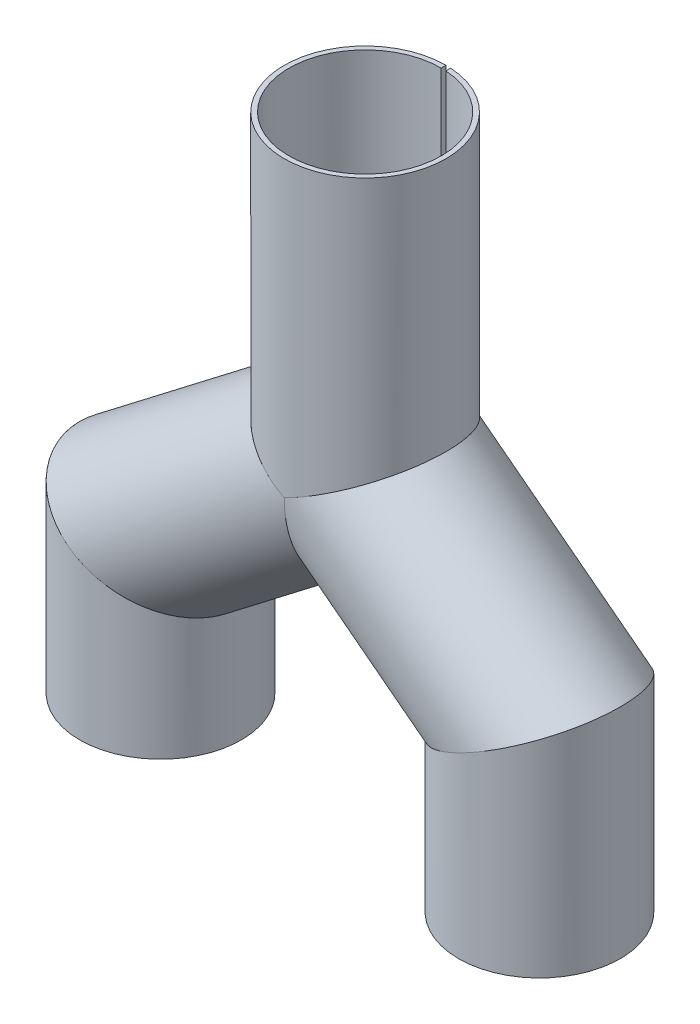
SolidWorks part; units mm, degrees
ref_plane "前视基准面" through (0, 0, 0) normal (0, 0, 1) x (1, 0, 0)
ref_plane "上视基准面" through (0, 0, 0) normal (0, 1, 0) x (1, 0, 0)
ref_plane "右视基准面" through (0, 0, 0) normal (1, 0, 0) x (0, 0, -1)
sketch "草图1" plane through (0, 0, 0) normal (0, 0, 1) x (1, 0, 0)
  line L0 (0, 0) -> (0, 61.6153) construction
  line L1 (-42.9378, -32.9568) -> (0, 0) construction
  line L2 (0, 0) -> (36.5871, -28.0823) construction
  line L3 (0, 0) -> (0, -65.4897) construction
  line L4 (0, -65.4897) -> (0, -66.4897) construction
  line L5 (-16.9772, 61.6153) -> (16.9772, 61.6153) construction
  line L6 (-42.9378, -32.9568) -> (-42.9378, -65.4897) construction
  line L7 (36.5871, -28.0823) -> (36.5871, -65.4897) construction
  line L8 (19.6099, -65.4897) -> (53.5642, -65.4897) construction
  line L9 (19.6099, -36.4531) -> (53.5642, -19.7116) construction
  line L10 (-25.9606, -41.3275) -> (-59.9149, -24.586) construction
  line L11 (-59.9149, -65.4897) -> (-25.9606, -65.4897) construction
  line L12 (16.9772, 61.6153) -> (16.9772, 8.3708) construction
  line L13 (16.9772, 8.3708) -> (53.5642, -19.7116) construction
  line L14 (53.5642, -19.7116) -> (53.5642, -65.4897) construction
  line L15 (19.6099, -65.4897) -> (19.6099, -36.4531) construction
  line L16 (19.6099, -36.4531) -> (0, -21.4015) construction
  line L17 (0, -21.4015) -> (-25.9606, -41.3275) construction
  line L18 (19.6099, -36.4531) -> (40.2837, -9.5181) construction
  line L19 (-16.9772, 61.6153) -> (-16.9772, 8.3708) construction
  line L20 (-16.9772, 8.3708) -> (-59.9149, -24.586) construction
  line L21 (-59.9149, -24.586) -> (-59.9149, -65.4897) construction
  line L22 (-25.9606, -41.3275) -> (-46.6344, -14.3926) construction
  line L23 (-16.9772, 8.3708) -> (0, 0) construction
  line L24 (0, 0) -> (16.9772, 8.3708) construction
  line L25 (-25.9606, -41.3275) -> (-25.9606, -65.4897) construction
  line L26 (0, 0) -> (0, 61.6153)
  dimension "t" = 1
  dimension "L1" = 61.6153
  dimension "R" = 16.9772
  dimension "L2" = 32.5329
  dimension "L4" = 42.9378
  dimension "L5" = 36.5871
  dimension "B" = 104.984
  dimension "B/2" = 52.492
sketch "草图2" plane through (0, 0, 0) normal (0, 1, 0) x (1, 0, 0)
  circle A0 centre (0, 0) radius 16.9772
extrude "拉伸-薄壁1" add sketch "草图2" along normal up to vertex (61.6153 mm away) thin up to point (0, 61.6153, 0) thin type one direction reverse wall 1
ref_plane "基准面1" through (36.5871, -28.0823, 0) normal (0.7933, -0.6089, 0) x (0, 0, -1)
sketch "草图3" plane through (36.5871, -28.0823, 0) normal (0.7933, -0.6089, 0) x (0, 0, -1)
  circle A0 centre (0, 0) radius 16.9772
extrude "拉伸-薄壁2" add sketch "草图3" against normal up to vertex (46.1219 mm away) and the other way up to vertex (8.3708 mm away) separate body thin up to point (0, 0, 0) other way up to point (53.5642, -19.7116, 0) thin type one direction reverse wall 1
ref_plane "基准面2" through (0, -65.4897, 0) normal (0, 1, 0) x (-1, 0, 0)
sketch "草图4" plane through (0, -65.4897, 0) normal (0, 1, 0) x (-1, 0, 0)
  line L0 (-19.6099, 0) -> (-53.5642, 0) construction
  circle A0 centre (-36.5871, 0) radius 16.9772
extrude "拉伸-薄壁3" add sketch "草图4" along normal up to vertex (45.7781 mm away) separate body thin up to point (53.5642, -19.7116, 0) thin type one direction reverse wall 1
ref_plane "基准面3" through (-42.9378, -32.9568, 0) normal (0.7933, 0.6089, 0) x (0, 0, -1)
sketch "草图5" plane through (-42.9378, -32.9568, 0) normal (0.7933, 0.6089, 0) x (0, 0, -1)
  circle A0 centre (0, 0) radius 16.9772
extrude "拉伸-薄壁4" add sketch "草图5" along normal up to vertex (54.1276 mm away) and the other way up to vertex (8.3708 mm away) separate body thin up to point (0, 0, 0) other way up to point (-59.9149, -24.586, 0) thin type one direction reverse wall 1
sketch "草图6" plane through (0, -65.4897, 0) normal (0, 1, 0) x (-1, 0, 0)
  circle A0 centre (42.9378, 0) radius 16.9772
extrude "拉伸-薄壁5" add sketch "草图6" along normal up to vertex (40.9036 mm away) separate body thin up to point (-59.9149, -24.586, 0) thin type one direction reverse wall 1
sketch "草图7" plane through (0, 0, 0) normal (0, 0, 1) x (1, 0, 0)
  line L0 (-33.9544, 16.7415) -> (0, 0)
  line L1 (0, 0) -> (33.9544, 16.7415)
  line L2 (33.9544, 16.7415) -> (33.9544, -19.7116)
  line L3 (33.9544, -19.7116) -> (-33.9544, -19.7116)
  line L4 (-33.9544, -19.7116) -> (-33.9544, 16.7415)
extrude "切除-拉伸1" cut sketch "草图7" against normal through all and the other way through all
sketch "草图8" plane through (0, 0, 0) normal (0, 0, 1) x (1, 0, 0)
  line L0 (-59.9149, -24.586) -> (-25.9606, -41.3275)
  line L2 (19.6099, -36.4531) -> (53.5642, -19.7116)
  line L3 (-59.9149, -24.586) -> (-59.9149, -66.4897)
  line L4 (-59.9149, -66.4897) -> (53.5642, -66.4897)
  line L5 (53.5642, -66.4897) -> (53.5642, -19.7116)
  line L6 (-25.9606, -41.3275) -> (-25.9606, -65.4897)
  line L7 (-25.9606, -65.4897) -> (19.6099, -65.4897)
  line L8 (19.6099, -65.4897) -> (19.6099, -36.4531)
extrude "切除-拉伸2" cut sketch "草图8" against normal through all and the other way through all
sketch "草图9" plane through (0, 0, 0) normal (0, 0, 1) x (1, 0, 0)
  line L0 (-16.9772, 8.3708) -> (0, 0) construction
  line L1 (-16.9772, 8.3708) -> (-16.9772, 61.6153)
  line L2 (0, 0) -> (0, -65.4897) construction
  line L3 (-16.9772, 61.6153) -> (16.9772, 61.6153)
  line L4 (16.9772, 61.6153) -> (16.9772, -65.4897)
  line L5 (-16.9772, 8.3708) -> (0, 0)
  line L6 (0, 0) -> (0, -65.4897)
  line L7 (0, -65.4897) -> (16.9772, -65.4897)
extrude "切除-拉伸3" cut sketch "草图9" against normal through all and the other way through all
sketch "草图10" plane through (0, 0, 0) normal (0, 0, 1) x (1, 0, 0)
  line L0 (16.9772, 8.3708) -> (16.9772, 61.6153)
  line L1 (16.9772, 61.6153) -> (-16.9772, 61.6153)
  line L2 (-16.9772, 61.6153) -> (-16.9772, -65.4897)
  line L3 (0, 0) -> (16.9772, 8.3708) construction
  line L4 (0, 0) -> (16.9772, 8.3708)
  line L5 (0, 0) -> (0, -65.4897) construction
  line L6 (0, 0) -> (0, -65.4897)
  line L7 (0, -65.4897) -> (-16.9772, -65.4897)
extrude "切除-拉伸6" cut sketch "草图10" against normal through all and the other way through all
extrude "切除-拉伸5" cut sketch "草图8<2>" against normal through all and the other way through all flip side to cut
sketch "草图8<2>" plane through (0, 0, 0) normal (0, 0, 1) x (1, 0, 0) same geometry as "草图8"
sketch "草图11" plane through (0, 0, 0) normal (0, 0, 1) x (1, 0, 0)
  line L0 (-42.9378, -32.9568) -> (0, 0) construction
  line L1 (-42.9378, -32.9568) -> (0, 0)
  line L2 (-42.9378, -32.9568) -> (-42.9378, -65.4897) construction
  line L3 (0, 0) -> (36.5871, -28.0823) construction
  line L4 (36.5871, -28.0823) -> (36.5871, -65.4897) construction
  line L5 (-42.9378, -32.9568) -> (-42.9378, -65.4897)
  line L6 (0, 0) -> (36.5871, -28.0823)
  line L7 (36.5871, -28.0823) -> (36.5871, -65.4897)
extrude "切除-拉伸-薄壁1" cut sketch "草图11" against normal through all flip side to cut thin thin type mid plane wall 1
extrude "切除-拉伸-薄壁2" cut sketch "草图1" against normal through all thin thin type one direction wall 1
equation "\"B/2@草图1\" = \"B@草图1\"/2"
equation "\"D5@拉伸-薄壁1\" = \"t@草图1\""
equation "\"D5@拉伸-薄壁2\" = \"t@草图1\""
equation "\"D5@拉伸-薄壁3\" = \"t@草图1\""
equation "\"D5@拉伸-薄壁4\" = \"t@草图1\""
equation "\"D5@拉伸-薄壁5\" = \"t@草图1\""
